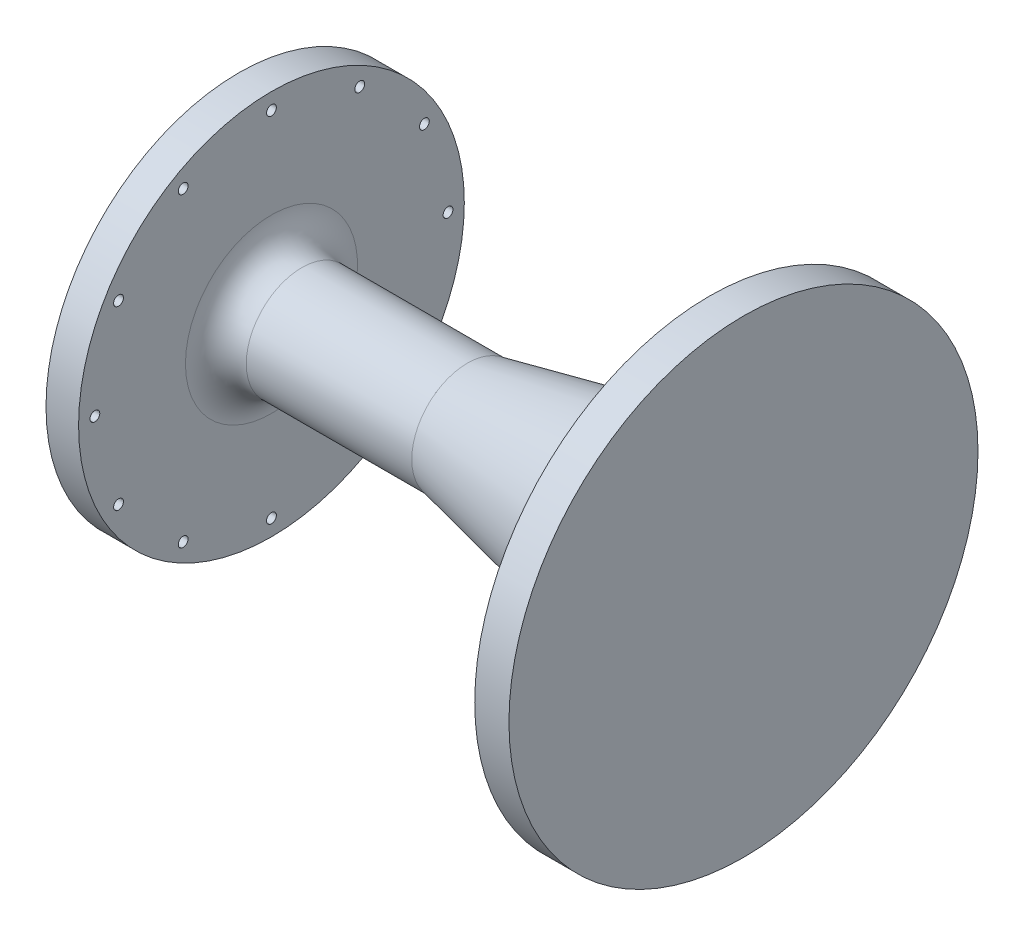
SolidWorks part; units mm, degrees
material "Stainless Steel (ferritic)"
ref_plane "Front Plane" through (0, 0, 0) normal (0, 0, 1) x (1, 0, 0)
ref_plane "Top Plane" through (0, 0, 0) normal (0, 1, 0) x (1, 0, 0)
ref_plane "Right Plane" through (0, 0, 0) normal (1, 0, 0) x (0, 0, -1)
sketch "Sketch2" plane through (0, 0, 0) normal (0, 0, 1) x (1, 0, 0)
  line L0 (0, 0) -> (165.0115, 0) construction
  line L1 (0, 20.5835) -> (0, 56.388)
  line L2 (0, 56.388) -> (9.525, 56.388)
  line L3 (9.525, 56.388) -> (9.525, 16.256)
  line L11 (66.8065, 16.256) -> (139.7, 31.75)
  line L17 (139.7, 31.75) -> (139.7, 29.5925)
  line L18 (60.325, 12.7208) -> (60.325, 14.351)
  line L19 (60.325, 14.351) -> (10.795, 14.351)
  line L20 (0, 20.5835) -> (10.795, 14.351)
  line L21 (60.325, 12.7208) -> (139.7, 29.5925)
  line L22 (9.525, 16.256) -> (66.8065, 16.256)
  dimension "D2" = 9.525
  dimension "D3" = 1.905
  dimension "D4" = 10.795
  dimension "D5" = 14.351
  dimension "D6" = 31.75
  dimension "D7" = 12
  dimension "D8" = 139.7
  dimension "D9" = 1.6302
  dimension "D10" = 30
  dimension "D11" = 56.388
  dimension "D12" = 49.53
revolve "Main Structure" add sketch "Sketch2" angle 360 about L0
sketch "Sketch4" plane through (0, 0, 0) normal (-1, 0, 0) x (0, 0, 1)
  circle A0 centre (0, 0) radius 51.6255 construction
  circle A1 centre (0, -51.6255) radius 2.146
  circle A2 centre (-25.8127, -44.709) radius 2.146
  circle A3 centre (-44.709, -25.8128) radius 2.146
  circle A4 centre (-51.6255, 0) radius 2.146
  circle A5 centre (-44.709, 25.8127) radius 2.146
  circle A6 centre (-25.8128, 44.709) radius 2.146
  circle A7 centre (0, 51.6255) radius 2.146
  circle A8 centre (25.8127, 44.709) radius 2.146
  circle A9 centre (44.709, 25.8128) radius 2.146
  circle A10 centre (51.6255, 0) radius 2.146
  circle A11 centre (44.709, -25.8127) radius 2.146
  circle A12 centre (25.8128, -44.709) radius 2.146
  point P29 (0, 0)
  dimension "D1" = 12
  dimension "D2" = 103.251
hole_wizard "Flange Holes" positions "Sketch7" profile "Sketch8" hole size "#33" standard "ANSI Inch" end condition up to next
sketch "Sketch7" plane through (0, 0, 0) normal (-1, 0, 0) x (0, 0, 1)
  point P0 (0, -51.6255)
  point P3 (-25.8127, -44.709)
  point P6 (-44.709, -25.8128)
  point P9 (-51.6255, 0)
  point P12 (-44.709, 25.8127)
  point P15 (-25.8128, 44.709)
  point P18 (0, 51.6255)
  point P21 (25.8127, 44.709)
  point P24 (44.709, 25.8128)
  point P27 (51.6255, 0)
  point P30 (44.709, -25.8127)
  point P33 (25.8128, -44.709)
sketch "Sketch8" plane through (0, -51.6255, 0) normal (0, 1, 0) x (0, 0, 1)
  line L0 (0, 0) -> (0, 9.525)
  line L1 (0, 9.525) -> (1.4351, 9.525)
  line L2 (1.4351, 9.525) -> (1.4351, 0)
  line L5 (1.4351, 0) -> (0, 0)
  line L11 (0, -6.35) -> (0, 107.95) construction
  dimension "Thru Hole Dia." = 2.8702
  dimension "Thru Hole Depth" = 9.525
sketch "Sketch9" plane through (0, 0, 0) normal (-1, 0, 0) x (0, 0, 1)
  line L0 (0, 0) -> (-67.6727, 18.1329) construction
  line L1 (0, 0) -> (-51.6255, 0) construction
  circle A0 centre (0, 0) radius 51.6255 construction
  circle A1 centre (-49.8664, 13.3617) radius 2.9451
  circle A2 centre (49.8664, -13.3617) radius 2.9451
  point P14 (0, 0)
  dimension "D1" = 15
  dimension "D2" = 2
hole_wizard "Dowel Holes" positions "Sketch10" profile "Sketch11" hole size "3/16" standard "ANSI Inch"
sketch "Sketch10" plane through (0, 0, 0) normal (-1, 0, 0) x (0, 0, 1)
  point P0 (49.8664, -13.3617)
  point P3 (-49.8664, 13.3617)
sketch "Sketch11" plane through (0, -13.3617, 49.8664) normal (0, 1, 0) x (0, 0, 1)
  line L0 (0, 0) -> (0, 7.7808)
  line L1 (0, 7.7808) -> (2.3812, 6.35)
  line L2 (2.3812, 6.35) -> (2.3812, 0)
  line L5 (2.3812, 0) -> (0, 0)
  line L10 (0, 7.7808) -> (-2.3812, 6.35) construction
  line L11 (0, -6.35) -> (0, 107.95) construction
  dimension "Hole Dia." = 4.7625
  dimension "Hole Depth" = 6.35
  dimension "Drill Angle" = 118
fillet "Fillet1" radius 8.89 1 edges at (9.525, 0, 16.256)
sketch "Sketch13" plane through (0, 0, 0) normal (0, 1, 0) x (1, 0, 0)
  line L0 (0, 36) -> (3.1496, 0)
  line L1 (0, 56.388) -> (0, -56.388) construction
  line L2 (3.1496, 0) -> (0, 0)
  line L3 (0, 0) -> (0, 36)
  dimension "D1" = 36
  dimension "D2" = 5
revolve "Cut-Revolve1" cut sketch "Sketch13" angle 360 about L2
chamfer "Chamfer1" distance 2.54 angle 45 1 edges at (139.7, 0, 31.75) first distance on face at (139.7, 0, 31.75)
sketch "Sketch14" plane through (9.525, 0, 0) normal (1, 0, 0) x (0, 0, -1)
  circle A0 centre (0, 0) radius 68.5667
extrude "Boss-Extrude1" add sketch "Sketch14" along normal blind 10 from offset 128
